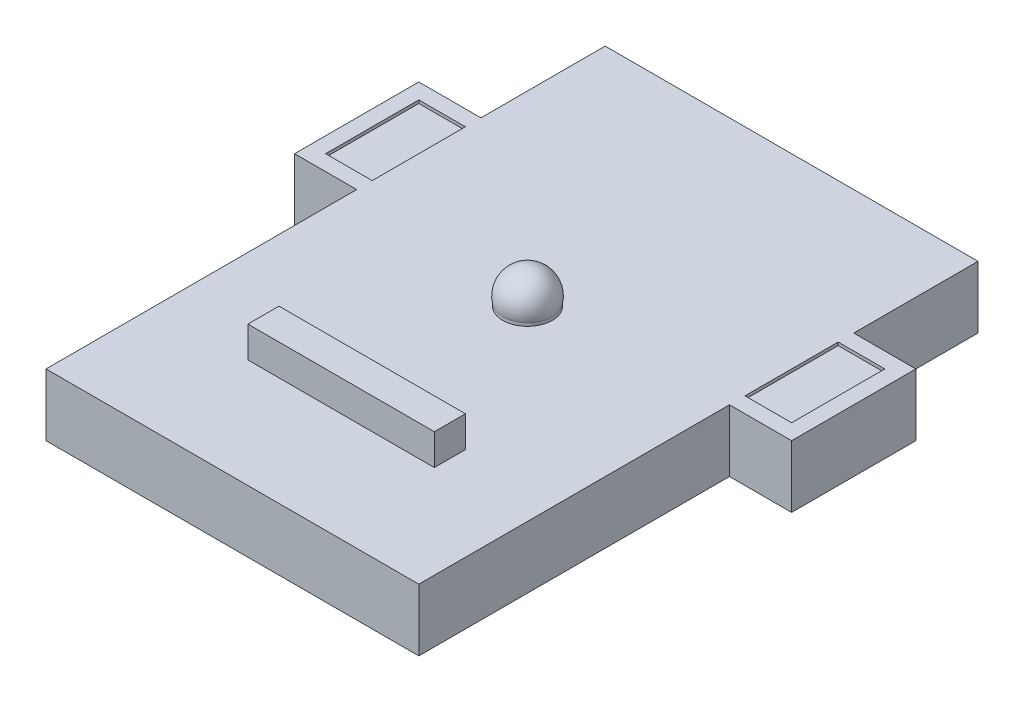
SolidWorks part; units mm, degrees
ref_plane "Front Plane" through (0, 0, 0) normal (0, 0, 1) x (1, 0, 0)
ref_plane "Top Plane" through (0, 0, 0) normal (0, 1, 0) x (1, 0, 0)
ref_plane "Right Plane" through (0, 0, 0) normal (1, 0, 0) x (0, 0, -1)
sketch "Sketch1" plane through (0, 0, 0) normal (0, 1, 0) x (1, 0, 0)
  line L1 (0, 0) -> (152.4, 0)
  line L2 (0, 0) -> (0, 228.6)
  line L3 (0, 228.6) -> (152.4, 228.6)
  line L4 (152.4, 0) -> (152.4, 228.6)
  dimension "D1" = 152.4
  dimension "D2" = 228.6
extrude "Boss-Extrude1" add sketch "Sketch1" along normal blind 25.4
sketch "Sketch5" plane through (0, 25.4, 0) normal (0, 1, 0) x (1, 0, 0)
  line L0 (152.4, 0) -> (152.4, 228.6) construction
  line L1 (152.4, 177.8) -> (177.8, 177.8)
  line L2 (152.4, 177.8) -> (152.4, 127)
  line L3 (152.4, 127) -> (177.8, 127)
  line L4 (177.8, 177.8) -> (177.8, 127)
  line L6 (0, 228.6) -> (0, 0) construction
  line L7 (0, 177.8) -> (-25.4, 177.8)
  line L8 (0, 177.8) -> (0, 127)
  line L9 (0, 127) -> (-25.4, 127)
  line L10 (152.4, 228.6) -> (0, 228.6) construction
  line L11 (-25.4, 177.8) -> (-25.4, 127)
  dimension "D1" = 50.8
  dimension "D2" = 25.4
  dimension "D3" = 50.8
  dimension "D4" = 50.8
  dimension "D5" = 50.8
  dimension "D6" = 25.4
extrude "Boss-Extrude5" add sketch "Sketch5" against normal up to surface (25.4 mm away) up to face at (76.2, 0, -114.3)
shell "Shell1" thickness 2.54 removed face at (76.2, 0, -139.7)
sketch "Sketch2" plane through (0, 25.4, 0) normal (0, 1, 0) x (1, 0, 0)
  line L0 (61.3833, 162.572) -> (91.0167, 162.572) construction
  line L1 (29.6333, 177.8) -> (61.3833, 177.8) construction
  line L2 (29.6333, 177.8) -> (29.6333, 146.05) construction
  line L3 (29.6333, 146.05) -> (61.3833, 146.05) construction
  line L4 (61.3833, 177.8) -> (61.3833, 146.05) construction
  line L5 (91.0167, 177.8) -> (122.7667, 177.8) construction
  line L6 (91.0167, 177.8) -> (91.0167, 146.05) construction
  line L7 (91.0167, 146.05) -> (122.7667, 146.05) construction
  line L8 (122.7667, 177.8) -> (122.7667, 146.05) construction
  line L9 (122.7667, 162.572) -> (152.4, 162.572) construction
  line L10 (152.4, 0) -> (152.4, 127) construction
  line L11 (29.6333, 164.91) -> (0, 164.91) construction
  line L12 (0, 228.6) -> (0, 177.8) construction
  line L13 (152.4, 228.6) -> (0, 228.6) construction
  dimension "D1" = 31.75
  dimension "D2" = 31.75
  dimension "D3" = 50.8
sketch "Sketch4" plane through (0, 25.4, 0) normal (0, 1, 0) x (1, 0, 0)
  line L0 (0, 0) -> (152.4, 0) construction
  line L1 (38.1, 57.15) -> (114.3, 57.15)
  line L2 (38.1, 57.15) -> (38.1, 44.45)
  line L3 (38.1, 44.45) -> (114.3, 44.45)
  line L4 (114.3, 57.15) -> (114.3, 44.45)
  point P6 (76.2, 57.15)
  point P7 (76.2, 0)
  dimension "D1" = 44.45
  dimension "D2" = 12.7
  dimension "D3" = 76.2
extrude "Boss-Extrude4" add sketch "Sketch4" along normal blind 12.7
sketch "Sketch3" plane through (0, 25.4, 0) normal (0, 1, 0) x (1, 0, 0)
  line L1 (0, 228.6) -> (0, 177.8) construction
  line L2 (91.0167, 146.05) -> (122.7667, 146.05) construction
  circle A0 centre (76.2, 120.65) radius 10.1211
  point P8 (117.5537, 146.05)
  dimension "D2" = 20.2421
  dimension "D3" = 76.2
  dimension "D1" = 25.4
extrude "Boss-Extrude3" add sketch "Sketch3" along normal blind 1.27
dome "Dome1" faces to dome 1 distance 12.7 reverse direction no elliptical dome no face at (76.2, 26.67, -110.5289) parameters "D1"=12.7
sketch "Sketch7" plane through (0, 25.4, 0) normal (0, 1, 0) x (1, 0, 0)
  line L0 (177.8, 177.8) -> (152.4, 177.8) construction
  line L1 (-19.05, 171.45) -> (0, 171.45)
  line L2 (-19.05, 171.45) -> (-19.05, 133.35)
  line L3 (-19.05, 133.35) -> (0, 133.35)
  line L4 (0, 171.45) -> (0, 133.35)
  line L5 (152.4, 171.45) -> (171.45, 171.45)
  line L6 (152.4, 171.45) -> (152.4, 133.35)
  line L7 (152.4, 133.35) -> (171.45, 133.35)
  line L8 (171.45, 171.45) -> (171.45, 133.35)
  line L9 (177.8, 127) -> (177.8, 177.8) construction
  line L10 (152.4, 127) -> (177.8, 127) construction
  line L11 (-25.4, 127) -> (0, 127) construction
  line L12 (0, 177.8) -> (-25.4, 177.8) construction
  line L13 (-25.4, 177.8) -> (-25.4, 127) construction
  line L14 (0, 228.6) -> (0, 177.8) construction
  line L15 (152.4, 177.8) -> (152.4, 228.6) construction
  dimension "D1" = 6.35
  dimension "D2" = 6.35
  dimension "D3" = 6.35
  dimension "D4" = 6.35
  dimension "D5" = 6.35
  dimension "D6" = 6.35
extrude "Cut-Extrude1" cut sketch "Sketch7" against normal blind 1.27
